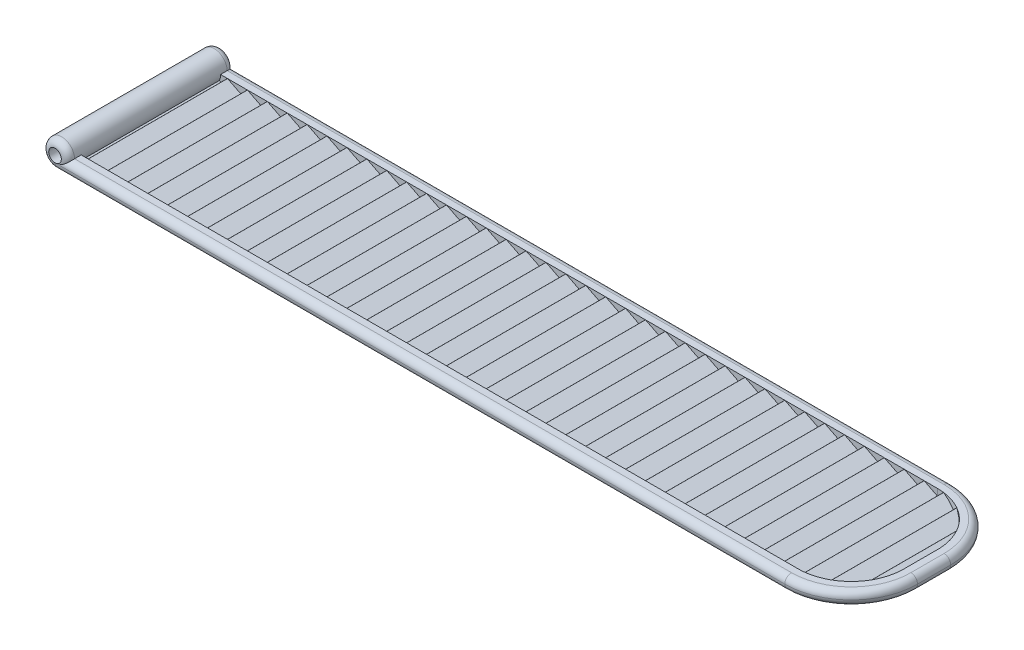
SolidWorks part; units mm, degrees
note: The reader was unsure of these and kept them because the rebuilt part matched: shared geometry of "Sketch4<3>".
ref_plane "Front Plane" through (0, 0, 0) normal (0, 0, 1) x (1, 0, 0)
ref_plane "Top Plane" through (0, 0, 0) normal (0, 1, 0) x (1, 0, 0)
ref_plane "Right Plane" through (0, 0, 0) normal (1, 0, 0) x (0, 0, -1)
sketch "Sketch1" plane through (0, 0, 0) normal (0, 1, 0) x (1, 0, 0)
  line L1 (0, 0) -> (110, 0)
  line L2 (0, 0) -> (0, 25)
  line L3 (0, 25) -> (110, 25)
  line L4 (120, 10) -> (120, 15)
  arc A0 (110, 0) -> (120, 10) centre (110, 10) ccw
  arc A1 (110, 25) -> (120, 15) centre (110, 15) cw
  dimension "D1" = 10
  dimension "D2" = 25
  dimension "D3" = 120
extrude "Boss-Extrude1" add sketch "Sketch1" along normal blind 2
sketch "Sketch2" plane through (0, 0, 0) normal (0, 0, 1) x (1, 0, 0)
  line L1 (0, 2) -> (110, 2) construction
  line L3 (0, 2) -> (2.99, 2)
  line L4 (107.99, 0.5) -> (107.99, 2)
  line L5 (0, 2) -> (2.99, 0.5)
  line L6 (2.99, 0.5) -> (2.99, 2)
  line L7 (5.99, 0.5) -> (5.99, 2)
  line L8 (3, 2) -> (5.99, 2)
  line L9 (3, 2) -> (5.99, 0.5)
  line L10 (8.99, 0.5) -> (8.99, 2)
  line L11 (6, 2) -> (8.99, 2)
  line L12 (6, 2) -> (8.99, 0.5)
  line L13 (11.99, 0.5) -> (11.99, 2)
  line L14 (9, 2) -> (11.99, 2)
  line L15 (9, 2) -> (11.99, 0.5)
  line L16 (14.99, 0.5) -> (14.99, 2)
  line L17 (12, 2) -> (14.99, 2)
  line L18 (12, 2) -> (14.99, 0.5)
  line L19 (17.99, 0.5) -> (17.99, 2)
  line L20 (15, 2) -> (17.99, 2)
  line L21 (15, 2) -> (17.99, 0.5)
  line L22 (20.99, 0.5) -> (20.99, 2)
  line L23 (18, 2) -> (20.99, 2)
  line L24 (18, 2) -> (20.99, 0.5)
  line L25 (23.99, 0.5) -> (23.99, 2)
  line L26 (21, 2) -> (23.99, 2)
  line L27 (21, 2) -> (23.99, 0.5)
  line L28 (26.99, 0.5) -> (26.99, 2)
  line L29 (24, 2) -> (26.99, 2)
  line L30 (24, 2) -> (26.99, 0.5)
  line L31 (29.99, 0.5) -> (29.99, 2)
  line L32 (27, 2) -> (29.99, 2)
  line L33 (27, 2) -> (29.99, 0.5)
  line L34 (32.99, 0.5) -> (32.99, 2)
  line L35 (30, 2) -> (32.99, 2)
  line L36 (30, 2) -> (32.99, 0.5)
  line L37 (35.99, 0.5) -> (35.99, 2)
  line L38 (33, 2) -> (35.99, 2)
  line L39 (33, 2) -> (35.99, 0.5)
  line L40 (38.99, 0.5) -> (38.99, 2)
  line L41 (36, 2) -> (38.99, 2)
  line L42 (36, 2) -> (38.99, 0.5)
  line L43 (41.99, 0.5) -> (41.99, 2)
  line L44 (39, 2) -> (41.99, 2)
  line L45 (39, 2) -> (41.99, 0.5)
  line L46 (44.99, 0.5) -> (44.99, 2)
  line L47 (42, 2) -> (44.99, 2)
  line L48 (42, 2) -> (44.99, 0.5)
  line L49 (47.99, 0.5) -> (47.99, 2)
  line L50 (45, 2) -> (47.99, 2)
  line L51 (45, 2) -> (47.99, 0.5)
  line L52 (50.99, 0.5) -> (50.99, 2)
  line L53 (48, 2) -> (50.99, 2)
  line L54 (48, 2) -> (50.99, 0.5)
  line L55 (53.99, 0.5) -> (53.99, 2)
  line L56 (51, 2) -> (53.99, 2)
  line L57 (51, 2) -> (53.99, 0.5)
  line L58 (56.99, 0.5) -> (56.99, 2)
  line L59 (54, 2) -> (56.99, 2)
  line L60 (54, 2) -> (56.99, 0.5)
  line L61 (59.99, 0.5) -> (59.99, 2)
  line L62 (57, 2) -> (59.99, 2)
  line L63 (57, 2) -> (59.99, 0.5)
  line L64 (62.99, 0.5) -> (62.99, 2)
  line L65 (60, 2) -> (62.99, 2)
  line L66 (60, 2) -> (62.99, 0.5)
  line L67 (65.99, 0.5) -> (65.99, 2)
  line L68 (63, 2) -> (65.99, 2)
  line L69 (63, 2) -> (65.99, 0.5)
  line L70 (68.99, 0.5) -> (68.99, 2)
  line L71 (66, 2) -> (68.99, 2)
  line L72 (66, 2) -> (68.99, 0.5)
  line L73 (71.99, 0.5) -> (71.99, 2)
  line L74 (69, 2) -> (71.99, 2)
  line L75 (69, 2) -> (71.99, 0.5)
  line L76 (74.99, 0.5) -> (74.99, 2)
  line L77 (72, 2) -> (74.99, 2)
  line L78 (72, 2) -> (74.99, 0.5)
  line L79 (77.99, 0.5) -> (77.99, 2)
  line L80 (75, 2) -> (77.99, 2)
  line L81 (75, 2) -> (77.99, 0.5)
  line L82 (80.99, 0.5) -> (80.99, 2)
  line L83 (78, 2) -> (80.99, 2)
  line L84 (78, 2) -> (80.99, 0.5)
  line L85 (83.99, 0.5) -> (83.99, 2)
  line L86 (81, 2) -> (83.99, 2)
  line L87 (81, 2) -> (83.99, 0.5)
  line L88 (86.99, 0.5) -> (86.99, 2)
  line L89 (84, 2) -> (86.99, 2)
  line L90 (84, 2) -> (86.99, 0.5)
  line L91 (89.99, 0.5) -> (89.99, 2)
  line L92 (87, 2) -> (89.99, 2)
  line L93 (87, 2) -> (89.99, 0.5)
  line L94 (92.99, 0.5) -> (92.99, 2)
  line L95 (90, 2) -> (92.99, 2)
  line L96 (90, 2) -> (92.99, 0.5)
  line L97 (95.99, 0.5) -> (95.99, 2)
  line L98 (93, 2) -> (95.99, 2)
  line L99 (93, 2) -> (95.99, 0.5)
  line L100 (98.99, 0.5) -> (98.99, 2)
  line L101 (96, 2) -> (98.99, 2)
  line L102 (96, 2) -> (98.99, 0.5)
  line L103 (101.99, 0.5) -> (101.99, 2)
  line L104 (99, 2) -> (101.99, 2)
  line L105 (99, 2) -> (101.99, 0.5)
  line L106 (104.99, 0.5) -> (104.99, 2)
  line L107 (102, 2) -> (104.99, 2)
  line L108 (102, 2) -> (104.99, 0.5)
  line L109 (105, 2) -> (107.99, 2)
  line L110 (105, 2) -> (107.99, 0.5)
  line L111 (110.99, 0.5) -> (110.99, 2)
  line L112 (108, 2) -> (110.99, 2)
  line L113 (108, 2) -> (110.99, 0.5)
  line L114 (113.99, 0.5) -> (113.99, 2)
  line L115 (111, 2) -> (113.99, 2)
  line L116 (111, 2) -> (113.99, 0.5)
  line L117 (116.99, 0.5) -> (116.99, 2)
  line L118 (114, 2) -> (116.99, 2)
  line L119 (114, 2) -> (116.99, 0.5)
  line L120 (119.99, 0.5) -> (119.99, 2)
  line L121 (117, 2) -> (119.99, 2)
  line L122 (117, 2) -> (119.99, 0.5)
  line L123 (122.99, 0.5) -> (122.99, 2)
  line L124 (120, 2) -> (122.99, 2)
  line L125 (120, 2) -> (122.99, 0.5)
  line L126 (125.99, 0.5) -> (125.99, 2)
  line L127 (123, 2) -> (125.99, 2)
  line L128 (123, 2) -> (125.99, 0.5)
  line L129 (128.99, 0.5) -> (128.99, 2)
  line L130 (126, 2) -> (128.99, 2)
  line L131 (126, 2) -> (128.99, 0.5)
  line L132 (131.99, 0.5) -> (131.99, 2)
  line L133 (129, 2) -> (131.99, 2)
  line L134 (129, 2) -> (131.99, 0.5)
  line L135 (134.99, 0.5) -> (134.99, 2)
  line L136 (132, 2) -> (134.99, 2)
  line L137 (132, 2) -> (134.99, 0.5)
  line L138 (137.99, 0.5) -> (137.99, 2)
  line L139 (135, 2) -> (137.99, 2)
  line L140 (135, 2) -> (137.99, 0.5)
  line L141 (140.99, 0.5) -> (140.99, 2)
  line L142 (138, 2) -> (140.99, 2)
  line L143 (138, 2) -> (140.99, 0.5)
  line L144 (143.99, 0.5) -> (143.99, 2)
  line L145 (141, 2) -> (143.99, 2)
  line L146 (141, 2) -> (143.99, 0.5)
  line L147 (146.99, 0.5) -> (146.99, 2)
  line L148 (144, 2) -> (146.99, 2)
  line L149 (144, 2) -> (146.99, 0.5)
  line L150 (149.99, 0.5) -> (149.99, 2)
  line L151 (147, 2) -> (149.99, 2)
  line L152 (147, 2) -> (149.99, 0.5)
  point P152 (0, 2)
  dimension "D1" = 1.5
  dimension "D2" = 2.99
  dimension "D3" = 50
extrude "Cut-Extrude2" cut sketch "Sketch2" against normal offset from surface (21 mm away) 2 from offset 2 up to face at (55, 1, -25) offset against normal yes
sketch "Sketch3" plane through (0, 2, 0) normal (0, 1, 0) x (1, 0, 0)
  line L1 (119.99, 15.4471) -> (119.99, 9.5529) construction
  line L2 (119.99, 15.4471) -> (119.99, 9.5529)
  line L3 (117.99, 15.3999) -> (117.99, 9.6001)
  line L4 (110, 25) -> (110, 23)
  line L5 (110, 0) -> (110, 2)
  arc A0 (110, 0) -> (116, 2) centre (110, 10) ccw construction
  arc A1 (116, 2) -> (116.99, 2.8488) centre (110, 10) ccw construction
  arc A2 (117, 2.8586) -> (119.99, 9.5529) centre (110, 10) ccw construction
  arc A3 (116, 23) -> (110, 25) centre (110, 15) ccw construction
  arc A4 (116.99, 22.1512) -> (116, 23) centre (110, 15) ccw construction
  arc A5 (119.99, 15.4471) -> (117, 22.1414) centre (110, 15) ccw construction
  arc A6 (110, 0) -> (116, 2) centre (110, 10) ccw
  arc A7 (116, 2) -> (117, 2.8586) centre (110, 10) ccw
  arc A8 (117, 2.8586) -> (119.99, 9.5529) centre (110, 10) ccw
  arc A9 (116, 23) -> (110, 25) centre (110, 15) ccw
  arc A10 (117, 22.1414) -> (116, 23) centre (110, 15) ccw
  arc A11 (119.99, 15.4471) -> (117, 22.1414) centre (110, 15) ccw
  arc A12 (115.6, 20.7131) -> (114.8, 21.4) centre (110, 15) ccw
  arc A13 (114.8, 21.4) -> (110, 23) centre (110, 15) ccw
  arc A14 (115.6, 4.2869) -> (117.99, 9.6001) centre (110, 10) ccw
  arc A15 (117.99, 15.3999) -> (115.6, 20.7131) centre (110, 15) ccw
  arc A16 (110, 2) -> (114.8, 3.6) centre (110, 10) ccw
  arc A17 (114.8, 3.6) -> (115.6, 4.2869) centre (110, 10) ccw
  arc A18 (115.592, 20.721) -> (114.8, 21.4) centre (110, 15) ccw construction
  arc A19 (114.8, 3.6) -> (115.592, 4.279) centre (110, 10) ccw construction
  arc A20 (116, 2) -> (116.99, 2.8488) centre (110, 10) ccw construction
  arc A21 (116.99, 22.1512) -> (116, 23) centre (110, 15) ccw construction
  point P1 (115.6029, 4.2897)
  point P7 (0, 0)
  point P27 (116.999, 2.8576)
  point P28 (115.598, 20.7131)
  point P31 (115.5971, 4.2869)
  dimension "D1" = 2
extrude "Boss-Extrude2" add sketch "Sketch3" against normal up to surface (2 mm away) up to face at (77.357, 0, -12.5)
sketch "Sketch4" plane through (0, 0, 0) normal (0, 0, 1) x (1, 0, 0)
  line L1 (0, 0) -> (110, 0) construction
  circle A0 centre (0, 1.95) radius 0.95
  circle A1 centre (0, 1.95) radius 1.95
  point P3 (-0.676, 2.6287)
  line M5 (110, 2) -> (0, 2)
  line M6 (0, 2) -> (0, 0)
  dimension "D1" = 1.9
  dimension "D2" = 1
extrude "Boss-Extrude3" add sketch "Sketch4" against normal up to surface (25 mm away) contours A1 A0 M5 M6 | A1 A0 M6 M5 | A0 M6 M5 | A0 M5 M6 up to face at (55, 1, -25)
extrude "Cut-Extrude3" cut sketch "Sketch4<3>" against normal up to surface (25 mm away) contours A0 M5 M6 | A0 M6 M5 up to face at (54.8946, 1.5778, -25)
sketch "Sketch4<3>" plane through (0, 0, 0) normal (0, 0, 1) x (1, 0, 0) same geometry as "Sketch4"
fillet "Fillet1" radius 1 12 edges at (-1.3964, 3.3111, -25) (-1.3964, 3.3111, 0) (55, 0, -25) (117.0711, 0, -22.0711) (120, 0, -12.5) (117.0711, 0, -2.9289) (55.9747, 2, -25) (117.0711, 2, -22.0711) (120, 2, -12.5) (117.0711, 2, -2.9289) (55, 0, 0) (55.9747, 2, 0)
